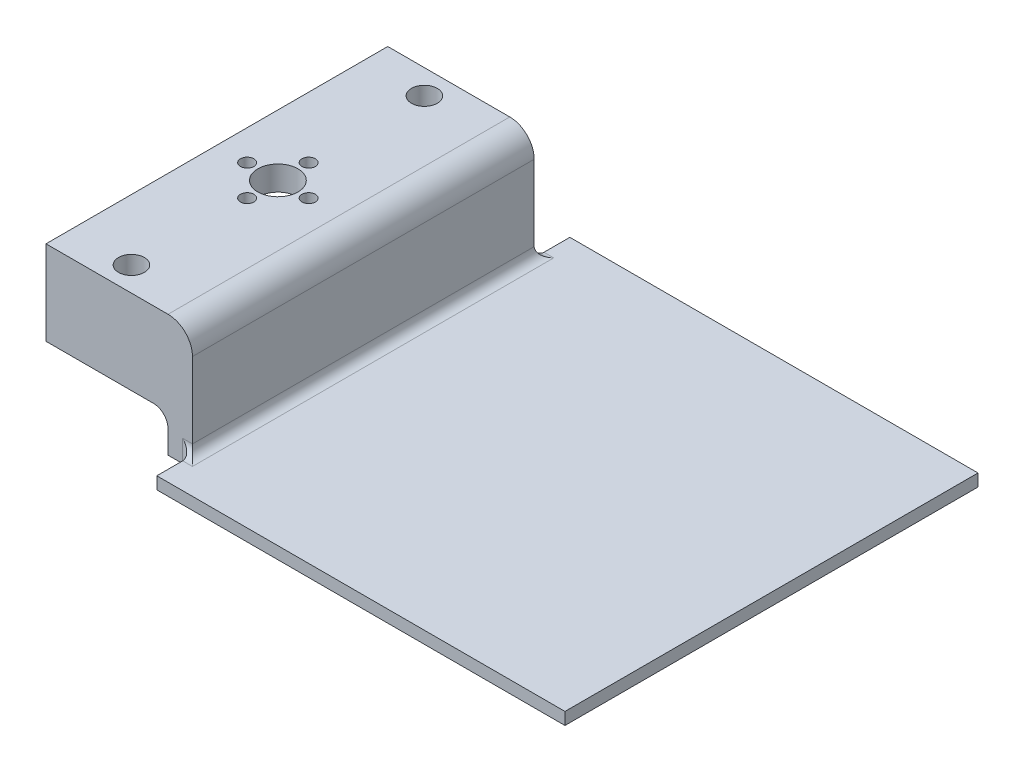
SolidWorks part; units mm, degrees
other "Markup1"
sketch "Sketch16" plane through (-31.975, 25.4, -53.721) normal (0, 1, 0) x (1, 0, 0)
ref_plane "Front Plane" through (0, 0, 0) normal (0, 0, 1) x (1, 0, 0)
ref_plane "Top Plane" through (0, 0, 0) normal (0, 1, 0) x (1, 0, 0)
ref_plane "Right Plane" through (0, 0, 0) normal (1, 0, 0) x (0, 0, -1)
sketch "Sketch1" plane through (0, 0, 0) normal (0, 1, 0) x (1, 0, 0)
  line L1 (0, -53.721) -> (106.172, -53.721)
  line L2 (0, -53.721) -> (0, 53.721)
  line L3 (0, 53.721) -> (106.172, 53.721)
  line L4 (106.172, -53.721) -> (106.172, 53.721)
  point P4 (0, 0)
  dimension "D1" = 107.442
  dimension "D2" = 106.172
extrude "Boss-Extrude1" add sketch "Sketch1" along normal blind 3.175
sketch "Sketch13" plane through (0, 0, 0) normal (0, 1, 0) x (1, 0, 0)
  line L0 (0, 53.721) -> (0, -53.721) construction
  line L1 (0, 44.45) -> (-38.1, 44.45)
  line L2 (0, 44.45) -> (0, -44.45)
  line L3 (0, -44.45) -> (-38.1, -44.45)
  line L4 (-38.1, 44.45) -> (-38.1, -44.45)
  point P9 (0, 0)
  dimension "D1" = 88.9
  dimension "D2" = 38.1
extrude "Boss-Extrude7" add sketch "Sketch13" along normal blind 31.75
sketch "Sketch15" plane through (0, 31.75, 0) normal (0, 1, 0) x (1, 0, 0)
  circle A0 centre (-22.225, -38.1) radius 3.2385 construction
  circle A1 centre (-22.225, 38.1) radius 3.2385 construction
  circle A6 centre (-22.225, -38.1) radius 3.2385 construction
  circle A7 centre (-22.225, 38.1) radius 3.2385 construction
  circle A8 centre (-22.225, 0) radius 2.6905 construction
  circle A9 centre (-22.225, 0) radius 2.6905 construction
  circle A10 centre (-22.225, 38.1) radius 3.3655
  circle A11 centre (-22.225, -38.1) radius 3.3655
  circle A12 centre (-22.225, 0) radius 5.227
  circle A13 centre (-14.225, 0) radius 1.75
  circle A14 centre (-22.225, -8) radius 1.75
  circle A15 centre (-30.225, 0) radius 1.75
  circle A16 centre (-22.225, 8) radius 1.75
  point P23 (-22.225, 0)
  dimension "D1" = 6.731
  dimension "D2" = 10.454
  dimension "D4" = 3.5
  dimension "D3" = 8
  dimension "D5" = 4
extrude "Cut-Extrude1" cut sketch "Sketch15" against normal through all
sketch "Sketch17" plane through (-38.1, 0, 0) normal (-1, 0, 0) x (0, 0, 1)
  line L0 (-44.45, 0) -> (44.45, 0) construction
  line L1 (31.75, 0) -> (-31.75, 0)
  line L2 (31.75, 0) -> (31.75, 25.4)
  line L3 (31.75, 25.4) -> (-31.75, 25.4)
  line L4 (-31.75, 0) -> (-31.75, 25.4)
  line L5 (-44.45, 31.75) -> (44.45, 31.75) construction
  point P6 (0, 0)
  dimension "D1" = 63.5
  dimension "D2" = 6.35
extrude "Cut-Extrude2" cut sketch "Sketch17" against normal offset from surface (31.75 mm away) 6.35 up to face at (0, 17.4625, 0)
sketch "Sketch18" plane through (0, 0, -44.45) normal (0, 0, -1) x (-1, 0, 0)
  line L0 (38.1, 31.75) -> (38.1, 0) construction
  line L1 (38.1, 9.779) -> (6.35, 9.779)
  line L2 (38.1, 9.779) -> (38.1, 0)
  line L3 (38.1, 0) -> (6.35, 0)
  line L4 (6.35, 9.779) -> (6.35, 0)
  line L5 (0, 0) -> (38.1, 0) construction
  line L7 (6.35, 0) -> (38.1, 0) construction
  dimension "D1" = 9.779
extrude "Cut-Extrude3" cut sketch "Sketch18" against normal through all
fillet "Fillet2" radius 12.7 2 edges at (-22.225, 25.4, 31.75) (-22.225, 25.4, -31.75)
fillet "Fillet1" radius 3.81 7 edges at (-6.35, 11.2395, 31.75) (-6.35, 25.4, 0) (-6.35, 11.2395, -31.75) (-6.35, 21.6803, 28.0303) (-6.35, 21.6803, -28.0303) (-6.35, 9.779, -38.1) (-6.35, 9.779, 38.1)
fillet "Fillet3" radius 2.54 1 edges at (0, 3.175, 0)
fillet "Fillet4" radius 2.54 4 edges at (1.27, 3.175, 44.45) (1.27, 3.175, -44.45) (0, 1.5875, 44.45) (0, 1.5875, -44.45)
fillet "Fillet5" radius 6.35 1 edges at (0, 31.75, 0)
equation "\"tightTol\" = 0.005in"
equation "\"normTol\"= 0.01in"
equation "\"looseTol\"= 0.02in"
equation "\"4.250000in-\"= 4.25"
equation "\"D1@Sketch1\"=4.25-\"looseTol\""
equation "\"D2@Sketch1\"=4.2in-\"looseTol\""
equation "\"D1@Sketch15\"=0.25+1.5*\"normTol\""
equation "\"D2@Sketch15\"=10.2mm+\"normTol\""
equation "\"D3@Sketch15\"=8mm"
equation "\"D4@Sketch15\"= 3.5mm"
equation "\"D1@Sketch18\"=0.375+\"normTol\""
